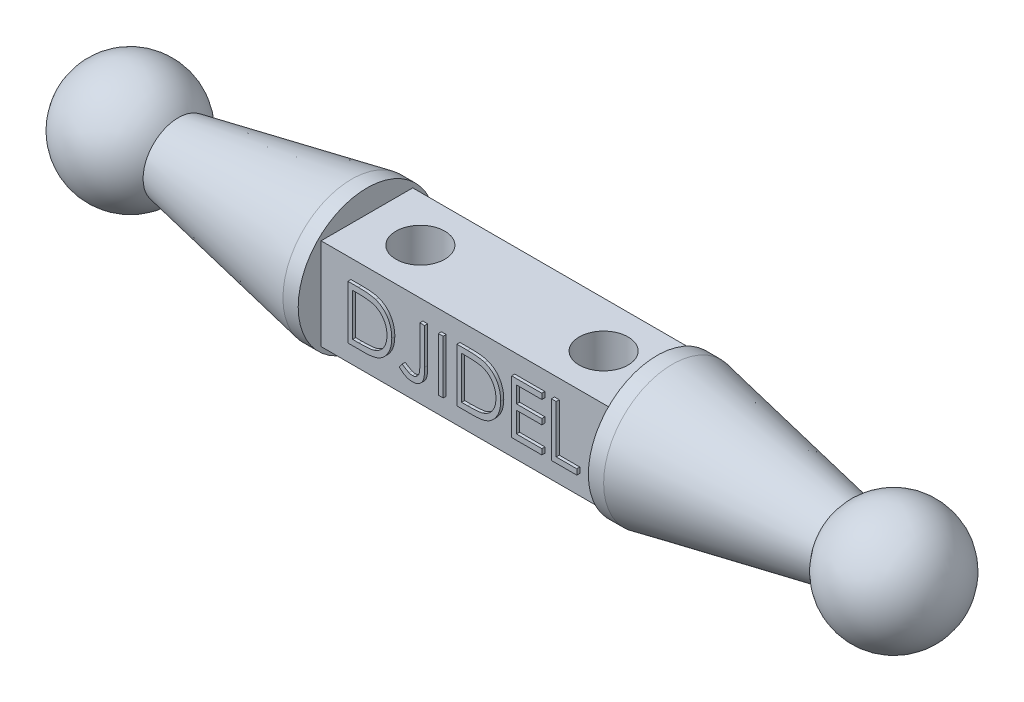
SolidWorks part; units mm, degrees
material "3.0255 (EN-AW 1350A)"
ref_plane "Plan de face" through (0, 0, 0) normal (0, 0, 1) x (1, 0, 0)
ref_plane "Plan de dessus" through (0, 0, 0) normal (0, 1, 0) x (1, 0, 0)
ref_plane "Plan de droite" through (0, 0, 0) normal (1, 0, 0) x (0, 0, -1)
sketch "Esquisse1" plane through (0, 0, 0) normal (0, 1, 0) x (1, 0, 0)
  line L0 (-27.9487, 0) -> (25, 0) construction
  line L1 (0, 19.1992) -> (0, -16.877) construction
  line L2 (10.5, 4.5) -> (21.9, 2.2948)
  line L3 (-9.5, 3) -> (9.5, 3)
  line L4 (0, 3) -> (0, 0)
  line L5 (25, 0) -> (37.3823, 0) construction
  line L6 (9.5, 3) -> (9.5, 0)
  line L7 (9.5, 4.5) -> (10.5, 4.5)
  line L8 (9.5, 4.5) -> (9.5, 0)
  line L9 (9.5, 0) -> (28.9, 0)
  line L10 (10.5, 4.5) -> (10.5, 0)
  line L11 (-9.5, 0) -> (-28.9, 0)
  line L12 (-9.5, 4.5) -> (-10.5, 4.5)
  line L13 (-9.5, 4.5) -> (-9.5, 0)
  line L14 (-10.5, 4.5) -> (-10.5, 0)
  line L15 (-10.5, 4.5) -> (-21.9, 2.2948)
  arc A0 (28.9, 0) -> (21.8532, 2.3038) centre (25, 0) ccw
  arc A1 (-28.9, 0) -> (-21.8532, 2.3038) centre (-25, 0) cw
  point P15 (9.5, 0)
  point P16 (9.5, 0)
  point P17 (0, 0)
  dimension "D1" = 11.4
  dimension "D2" = 7.8
  dimension "D3" = 9.5
  dimension "D4" = 3
  dimension "D5" = 4.5
  dimension "D6" = 1
  dimension "D7" = 10.948
  dimension "D8" = 25
revolve "Révolution1" add sketch "Esquisse1" angle 360 about L0 region at (-10, 0, -2.25) region at (10, 0, -2.25) region at (19.1256, 0, -1.7362) region at (-19.1256, 0, -1.7362)
sketch "Esquisse4" plane through (0, 0, 0) normal (1, 0, 0) x (0, 0, -1)
  line L1 (3, -3) -> (-3, -3)
  line L2 (3, -3) -> (3, 3)
  line L3 (3, 3) -> (-3, 3)
  line L4 (-3, -3) -> (-3, 3)
  line L5 (3, -3) -> (-3, 3) construction
  line L6 (3, 3) -> (-3, -3) construction
  point P0 (0, 0)
  dimension "D1" = 6
  dimension "D2" = 6
extrude "Boss.-Extru.1" add sketch "Esquisse4" along normal blind 9.5 and the other way blind 9.5
sketch "Esquisse5" plane through (0, 3, 0) normal (0, 1, 0) x (1, 0, 0)
  line L0 (-9.5, 0) -> (9.5, 0) construction
  line L1 (-9.5, -4.5) -> (-9.5, 4.5) construction
  line L2 (9.5, 3) -> (9.5, -3) construction
  line L3 (-6, 0) -> (6, 0)
  circle A0 centre (6, 0) radius 1.6
  circle A1 centre (-6, 0) radius 1.6
  point P10 (0, 0)
  dimension "D1" = 3.2
  dimension "D2" = 3.2
  dimension "D3" = 12
extrude "Enlèv. mat.-Extru.1" cut sketch "Esquisse5" against normal blind 9.5 contours A1 L0 L3 | L0 A1 L3 | L3 L0 A0 | L0 L3 A0 region at (-6, 3, -0.6791) region at (-6, 3, 0.6791) region at (6, 3, -0.6791) region at (6, 3, 0.6791)
sketch "Esquisse6" plane through (0, 0, 3) normal (0, 0, 1) x (1, 0, 0)
  text T0 "DJIDEL"
extrude "Boss.-Extru.2" add sketch "Esquisse6" along normal blind 0.2 separate body
